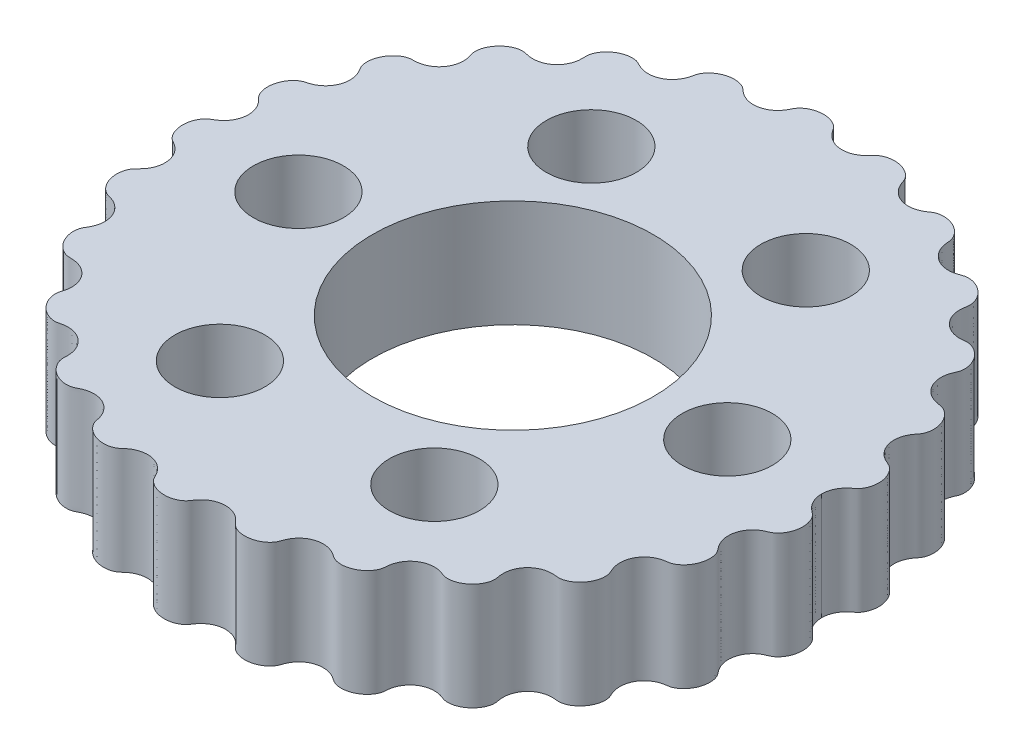
SolidWorks part; units mm, degrees
ref_plane "Front Plane" through (0, 0, 0) normal (0, 0, 1) x (1, 0, 0)
ref_plane "Top Plane" through (0, 0, 0) normal (0, 1, 0) x (1, 0, 0)
ref_plane "Right Plane" through (0, 0, 0) normal (1, 0, 0) x (0, 0, -1)
sketch "Sketch2" plane through (0, 0, 0) normal (0, 1, 0) x (1, 0, 0)
  line L0 (-15.4, 0) -> (14.4, 0) construction
  line L1 (0, 0) -> (0, 14.9128) construction
  line L2 (0, 0) -> (0, -14.9128) construction
  line L3 (0, 0) -> (-0.5, 0) construction
  line L4 (-0.5, 0) -> (-0.5, 15.3103) construction
  line L5 (-0.5, 0) -> (-0.5, -15.3103) construction
  line L6 (14.4, 0) -> (15.5, 0) construction
  line L7 (0, 0) -> (10, 0) construction
  line L8 (7.9, 0) -> (9.5, 0)
  line L9 (-0.5, 0) -> (9.5, 0) construction
  circle A0 centre (-0.5, 0) radius 16
  circle A1 centre (15.5, 0) radius 1
  circle A2 centre (15.0351, -3.8291) radius 1
  circle A3 centre (13.6673, -7.4356) radius 1
  circle A4 centre (11.4762, -10.61) radius 1
  circle A5 centre (8.589, -13.1677) radius 1
  circle A6 centre (5.1737, -14.9603) radius 1
  circle A7 centre (1.4286, -15.8833) radius 1
  circle A8 centre (-2.4286, -15.8833) radius 1
  circle A9 centre (-6.1737, -14.9603) radius 1
  circle A10 centre (-9.589, -13.1677) radius 1
  circle A11 centre (-12.4762, -10.61) radius 1
  circle A12 centre (-14.6673, -7.4356) radius 1
  circle A13 centre (-16.0351, -3.8291) radius 1
  circle A14 centre (-16.5, 0) radius 1
  circle A15 centre (-16.0351, 3.8291) radius 1
  circle A16 centre (-14.6673, 7.4356) radius 1
  circle A17 centre (-12.4762, 10.61) radius 1
  circle A18 centre (-9.589, 13.1677) radius 1
  circle A19 centre (-6.1737, 14.9603) radius 1
  circle A20 centre (-2.4286, 15.8833) radius 1
  circle A21 centre (1.4286, 15.8833) radius 1
  circle A22 centre (5.1737, 14.9603) radius 1
  circle A23 centre (8.589, 13.1677) radius 1
  circle A24 centre (11.4762, 10.61) radius 1
  circle A25 centre (13.6673, 7.4356) radius 1
  circle A26 centre (15.0351, 3.8291) radius 1
  circle A27 centre (0, 0) radius 10
  circle A28 centre (10, 0) radius 2.1
  circle A29 centre (5, -8.6603) radius 2.1
  circle A30 centre (-5, -8.6603) radius 2.1
  circle A31 centre (-10, 0) radius 2.1
  circle A32 centre (-5, 8.6603) radius 2.1
  circle A33 centre (5, 8.6603) radius 2.1
  circle A34 centre (-6, 8.6603) radius 2.1
  circle A35 centre (4, 8.6603) radius 2.1
  circle A36 centre (9, 0) radius 2.1
  circle A37 centre (4, -8.6603) radius 2.1
  circle A38 centre (-6, -8.6603) radius 2.1
  circle A39 centre (-1, 0) radius 10
  circle A40 centre (-11, 0) radius 2.1
  circle A41 centre (9.5, 0) radius 1.5
  circle A42 centre (4.5, -8.6603) radius 1.5
  circle A43 centre (-5.5, -8.6603) radius 1.5
  circle A44 centre (-10.5, 0) radius 1.5
  circle A45 centre (-5.5, 8.6603) radius 1.5
  circle A46 centre (4.5, 8.6603) radius 1.5
  circle A47 centre (0, 0) radius 5.55
  spline S0 degree 4 poles (14.1521, 3.1658) (14.188, 3.1199) (14.2658, 3.0332) (14.3775, 2.9384) (14.515, 2.8555) (14.6203, 2.806) (14.6874, 2.778) (14.7412, 2.7556) (14.7939, 2.7309) (14.8442, 2.7016) (14.9616, 2.6171) (15.116, 2.4418) (15.2531, 2.163) (15.3044, 1.8261) (15.2781, 1.5454) (15.2134, 1.3341) (15.1457, 1.199) (15.0717, 1.0959) (14.999, 1.0246) (14.9346, 0.9749) (14.8529, 0.9144) (14.7598, 0.8351) (14.6613, 0.7318) (14.5658, 0.5985) (14.4899, 0.4547) (14.4445, 0.3242) (14.4198, 0.2202) (14.4058, 0.1237) (14.3997, 0.036) (14.399, -0.0233) (14.4055, -0.1232) (14.4175, -0.2057) (14.4353, -0.2848) (14.4589, -0.3638) (14.4955, -0.4601) (14.5538, -0.5777) (14.629, -0.6905) (14.7205, -0.7952) (14.8099, -0.8785) (14.886, -0.9397) (14.9653, -0.9969) (15.0394, -1.0608) (15.1018, -1.1365) (15.1543, -1.2193) (15.2086, -1.3292) (15.2563, -1.4688) (15.2881, -1.6381) (15.2945, -1.881) (15.2523, -2.1199) (15.1638, -2.3444) (15.0424, -2.5231) (14.9425, -2.6287) (14.8453, -2.7036) (14.7572, -2.7504) (14.6644, -2.7867) (14.5734, -2.827) (14.4636, -2.8857) (14.309, -2.9902) (14.1305, -3.1658) (13.9721, -3.435) (13.894, -3.7733) (13.9169, -4.0803) (13.9952, -4.3102) (14.0824, -4.4685) (14.1503, -4.5677) (14.21, -4.6429) (14.2706, -4.7176) (14.3202, -4.8002) (14.3654, -4.9109) (14.3993, -5.0496) (14.4169, -5.2624) (14.3843, -5.5009) (14.3041, -5.731) (14.178, -5.9418) (14.0479, -6.0957) (13.9108, -6.2086) (13.7771, -6.2844) (13.6546, -6.3259) (13.5506, -6.3413) (13.4467, -6.3556) (13.3441, -6.3782) (13.2186, -6.4164) (13.0491, -6.4902) (12.8504, -6.6239) (12.6494, -6.8484) (12.5061, -7.1523) (12.463, -7.451) (12.49, -7.6921) (12.5392, -7.8624) (12.5803, -7.968) (12.6183, -8.0504) (12.6544, -8.1336) (12.6783, -8.2214) (12.6929, -8.336) (12.6907, -8.4762) (12.6543, -8.6855) (12.5452, -8.9512) (12.3731, -9.1837) (12.1492, -9.3663) (11.9533, -9.4633) (11.8116, -9.5062) (11.6867, -9.5225) (11.5835, -9.517) (11.4812, -9.5034) (11.3782, -9.4969) (11.2749, -9.4982) (11.1721, -9.508) (11.0085, -9.5382) (10.791, -9.6158) (10.5438, -9.7787) (10.3474, -10.0243) (10.2402, -10.2686) (10.1943, -10.4842) (10.1853, -10.6384) (10.1931, -10.7705) (10.2091, -10.8795) (10.2256, -10.9662) (10.236, -11.0539) (10.2331, -11.1423) (10.2158, -11.2534) (10.1767, -11.3842) (10.0886, -11.5718) (9.9146, -11.8006) (9.6439, -12.0158) (9.3384, -12.1314) (9.0923, -12.1519) (8.9388, -12.1247) (8.8741, -12.1049) (8.8233, -12.0863) (8.76, -12.0622) (8.6577, -12.0268) (8.5127, -11.9913) (8.2954, -11.971) (8.0233, -12.0058) (7.7397, -12.12) (7.4775, -12.3303) (7.3093, -12.5758) (7.2277, -12.7964) (7.1948, -12.9647) (7.1831, -13.0729) (7.1774, -13.16) (7.1639, -13.2682) (7.1207, -13.3961) (7.0432, -13.5357) (6.8963, -13.7154) (6.6678, -13.8963) (6.3478, -14.0387) (6.02, -14.0727) (5.7619, -14.0269) (5.5985, -13.9438) (5.5126, -13.8801) (5.4018, -13.8057) (5.2599, -13.7303) (5.0524, -13.6565) (4.7738, -13.623) (4.4626, -13.6683) (4.1888, -13.7999) (3.9912, -13.9665) (3.8578, -14.1339) (3.7826, -14.2632) (3.7309, -14.3799) (3.6959, -14.48) (3.6689, -14.5606) (3.6251, -14.6573) (3.5494, -14.7647) (3.44, -14.8752) (3.2557, -15.006) (2.9928, -15.1201) (2.6515, -15.1757) (2.3406, -15.1291) (2.1258, -15.0338) (2.011, -14.9468) (1.9698, -14.909) (1.9317, -14.8681) (1.8954, -14.8255) (1.8499, -14.7726) (1.7735, -14.691) (1.6576, -14.5893) (1.4677, -14.4687) (1.2013, -14.3748) (0.8943, -14.3518) (0.5705, -14.4236) (0.3173, -14.5632) (0.1515, -14.7141) (0.0481, -14.8418) (-0.0114, -14.9289) (-0.057, -15) (-0.1205, -15.0845) (-0.2167, -15.1711) (-0.3455, -15.2521) (-0.5484, -15.3356) (-0.8128, -15.3854) (-1.084, -15.3726) (-1.345, -15.2972) (-1.5435, -15.1922) (-1.6658, -15.0976) (-1.7547, -15.002) (-1.8112, -14.9128) (-1.8483, -14.8369) (-1.8948, -14.7422) (-1.9811, -14.5964) (-2.1305, -14.4153) (-2.3717, -14.2374) (-2.6941, -14.1243) (-3.0058, -14.1121) (-3.2798, -14.1742) (-3.4814, -14.2713) (-3.6077, -14.3581) (-3.6929, -14.4296) (-3.7443, -14.4763) (-3.7855, -14.5136) (-3.839, -14.5578) (-3.9718, -14.6426) (-4.2092, -14.7163) (-4.5379, -14.7232) (-4.871, -14.6233) (-5.1192, -14.4741) (-5.2872, -14.3161) (-5.3818, -14.1887) (-5.4416, -14.0686) (-5.4698, -13.9639) (-5.4862, -13.8788) (-5.5106, -13.7734) (-5.5628, -13.6112) (-5.6686, -13.4029) (-5.8615, -13.1808) (-6.1409, -13.0036) (-6.4324, -12.9205) (-6.707, -12.9139) (-6.9246, -12.958) (-7.0705, -13.0119) (-7.1719, -13.0612) (-7.2342, -13.0943) (-7.2842, -13.1203) (-7.3485, -13.1494) (-7.4504, -13.1813) (-7.5929, -13.1993) (-7.8225, -13.1875) (-8.1082, -13.1019) (-8.3607, -12.9481) (-8.5641, -12.7393) (-8.6869, -12.541) (-8.7459, -12.3913) (-8.7711, -12.2579) (-8.7697, -12.1482) (-8.7645, -12.0606) (-8.7633, -11.951) (-8.7731, -11.8212) (-8.8019, -11.6732) (-8.8729, -11.4717) (-9.0045, -11.25) (-9.2205, -11.0351) (-9.4997, -10.8905) (-9.7475, -10.8369) (-9.9383, -10.8322) (-10.0675, -10.8437) (-10.1698, -10.8609) (-10.2704, -10.8859) (-10.3717, -10.9089) (-10.4995, -10.9144) (-10.6499, -10.893) (-10.8644, -10.8236) (-11.1154, -10.6702) (-11.3185, -10.4608) (-11.4614, -10.2119) (-11.5248, -10.0134) (-11.5464, -9.8777) (-11.5487, -9.7646) (-11.5393, -9.6761) (-11.5169, -9.5902) (-11.4896, -9.5058) (-11.4606, -9.3988) (-11.4371, -9.2678) (-11.428, -9.1126) (-11.4489, -8.8917) (-11.5253, -8.6444) (-11.6806, -8.3917) (-11.9083, -8.1893) (-12.1461, -8.0664) (-12.3515, -8.0112) (-12.509, -7.9918) (-12.6408, -7.9895) (-12.7466, -7.9882) (-12.8744, -7.9638) (-13.0178, -7.9059) (-13.1692, -7.8114) (-13.319, -7.6747) (-13.472, -7.4805) (-13.5815, -7.2609) (-13.644, -7.0266) (-13.6529, -6.8129) (-13.6365, -6.6728) (-13.6064, -6.5605) (-13.5704, -6.4764) (-13.5232, -6.3982) (-13.4752, -6.3206) (-13.4215, -6.2199) (-13.3522, -6.0556) (-13.2972, -5.8178) (-13.3061, -5.5112) (-13.4183, -5.1858) (-13.5996, -4.9373) (-13.7884, -4.7826) (-13.9504, -4.6931) (-14.068, -4.6441) (-14.1647, -4.6121) (-14.2634, -4.587) (-14.3606, -4.5562) (-14.4721, -4.4972) (-14.5906, -4.4054) (-14.7415, -4.2409) (-14.8856, -3.984) (-14.9605, -3.7) (-14.9625, -3.4094) (-14.9171, -3.1994) (-14.8649, -3.0655) (-14.8048, -2.9613) (-14.7437, -2.886) (-14.6735, -2.8194) (-14.6048, -2.7515) (-14.5411, -2.6786) (-14.4829, -2.6013) (-14.3984, -2.4684) (-14.3099, -2.2678) (-14.2572, -1.9916) (-14.2948, -1.6527) (-14.4157, -1.3725) (-14.5648, -1.1806) (-14.7009, -1.0585) (-14.8015, -0.9857) (-14.886, -0.9336) (-14.9732, -0.8861) (-15.056, -0.8309) (-15.1453, -0.7457) (-15.2341, -0.6279) (-15.3021, -0.4979) (-15.3506, -0.3595) (-15.3784, -0.2422) (-15.3932, -0.1473) (-15.4005, -0.0379) (-15.4007, 0.0312) (-15.3943, 0.133) (-15.3819, 0.2227) (-15.3632, 0.3082) (-15.3383, 0.3938) (-15.2991, 0.498) (-15.241, 0.614) (-15.1569, 0.7356) (-15.0521, 0.8388) (-14.947, 0.9) (-14.8417, 0.9596) (-14.7374, 1.0292) (-14.6222, 1.1253) (-14.4762, 1.2888) (-14.3483, 1.5104) (-14.2696, 1.788) (-14.2718, 2.0824) (-14.3338, 2.3297) (-14.4228, 2.5131) (-14.5089, 2.6398) (-14.5912, 2.7371) (-14.6628, 2.8095) (-14.7315, 2.8736) (-14.7874, 2.9388) (-14.8392, 3.0187) (-14.9, 3.1445) (-14.933, 3.2628) (-14.9484, 3.3663) (-14.9531, 3.4358) knots 0 0 0 0 0 0.003662 0.007324 0.009155 0.010071 0.010986 0.011902 0.012818 0.013733 0.014649 0.020984 0.02732 0.032959 0.035778 0.038598 0.041156 0.042436 0.043715 0.044995 0.046274 0.048833 0.051398 0.053964 0.05653 0.059096 0.059963 0.060831 0.062566 0.06386 0.065154 0.066448 0.067743 0.069037 0.070331 0.072919 0.075992 0.077529 0.079065 0.080602 0.082139 0.083675 0.085212 0.086754 0.088296 0.09138 0.094464 0.097548 0.103529 0.106519 0.10951 0.111075 0.112641 0.114207 0.115773 0.117339 0.118905 0.122036 0.127492 0.132948 0.138255 0.143562 0.146585 0.148096 0.149608 0.151119 0.15263 0.154142 0.155653 0.158618 0.161583 0.167513 0.170668 0.173824 0.176979 0.180135 0.181785 0.183435 0.185086 0.186736 0.188387 0.190037 0.193338 0.198334 0.203329 0.208757 0.214186 0.217039 0.218465 0.219892 0.221319 0.222745 0.224172 0.225598 0.228568 0.231538 0.237477 0.243509 0.246525 0.249541 0.251164 0.252787 0.25441 0.256033 0.257656 0.259279 0.260902 0.262525 0.268116 0.273708 0.279232 0.281995 0.284757 0.287531 0.288919 0.290306 0.291693 0.293081 0.294468 0.295855 0.298752 0.301648 0.307441 0.313806 0.320171 0.321875 0.322726 0.323578 0.32443 0.325282 0.326985 0.330392 0.333799 0.338942 0.344084 0.349371 0.354658 0.3574 0.358771 0.360142 0.361513 0.362884 0.365627 0.368572 0.371516 0.377406 0.383828 0.390249 0.39193 0.393611 0.395291 0.396972 0.400333 0.403695 0.409076 0.414457 0.419833 0.422521 0.425209 0.427878 0.429213 0.430548 0.431883 0.433218 0.435887 0.438758 0.441629 0.44737 0.453781 0.460191 0.46107 0.46195 0.462829 0.463708 0.464587 0.465466 0.467225 0.470742 0.474259 0.479542 0.484825 0.489836 0.494847 0.497504 0.498832 0.500161 0.501489 0.502818 0.505475 0.508247 0.51102 0.516564 0.52227 0.525123 0.527976 0.530631 0.531959 0.533286 0.534614 0.535941 0.538597 0.543936 0.549276 0.554531 0.559787 0.563284 0.566782 0.568531 0.569405 0.570279 0.571154 0.572028 0.573777 0.580153 0.586529 0.592383 0.595311 0.598238 0.600963 0.602326 0.603688 0.605051 0.606414 0.609139 0.614393 0.619646 0.62466 0.629675 0.633224 0.636772 0.638547 0.639434 0.640321 0.641208 0.642095 0.64387 0.647026 0.650182 0.656494 0.66242 0.665383 0.668345 0.671105 0.672484 0.673864 0.675243 0.676623 0.679382 0.682041 0.684701 0.690021 0.695473 0.700926 0.704188 0.705819 0.70745 0.709081 0.710712 0.712344 0.713975 0.717095 0.720216 0.726458 0.732287 0.735201 0.738116 0.739511 0.740907 0.742302 0.743698 0.745093 0.746488 0.749279 0.752059 0.754839 0.760398 0.765424 0.770449 0.773769 0.777088 0.778748 0.780408 0.782068 0.783727 0.786901 0.790075 0.793249 0.796422 0.802397 0.805385 0.808372 0.809808 0.811244 0.812679 0.814115 0.81555 0.816986 0.819857 0.825318 0.830779 0.83599 0.841201 0.844404 0.846006 0.847607 0.849209 0.850811 0.852412 0.854014 0.857107 0.8602 0.866387 0.872353 0.875336 0.878319 0.87984 0.881361 0.882882 0.884402 0.885923 0.887444 0.888965 0.890486 0.895823 0.90116 0.906397 0.911634 0.914757 0.916319 0.91788 0.919441 0.921003 0.922564 0.924126 0.927182 0.930238 0.931767 0.933295 0.934823 0.936351 0.937751 0.93915 0.940549 0.941949 0.943348 0.944747 0.947546 0.950087 0.952628 0.953898 0.955168 0.957709 0.960509 0.96331 0.96891 0.973663 0.978415 0.981621 0.984826 0.986428 0.988031 0.989634 0.991236 0.992332 0.993427 0.995618 1 1 1 1 1 construction
  spline S1 degree 4 poles (14.4, 0) (14.4, -0.018) (14.401, -0.0542) (14.4055, -0.1232) (14.4175, -0.2057) (14.4353, -0.2848) (14.4589, -0.3638) (14.4955, -0.4601) (14.5538, -0.5777) (14.629, -0.6905) (14.7205, -0.7952) (14.8099, -0.8785) (14.886, -0.9397) (14.9653, -0.9969) (15.0394, -1.0608) (15.1018, -1.1365) (15.1543, -1.2193) (15.2086, -1.3292) (15.2563, -1.4688) (15.2881, -1.6381) (15.2945, -1.881) (15.2523, -2.1199) (15.1638, -2.3444) (15.0424, -2.5231) (14.9425, -2.6287) (14.8453, -2.7036) (14.7572, -2.7504) (14.6644, -2.7867) (14.5734, -2.827) (14.4636, -2.8857) (14.309, -2.9902) (14.1305, -3.1658) (13.9721, -3.435) (13.894, -3.7733) (13.9169, -4.0803) (13.9952, -4.3102) (14.0824, -4.4685) (14.1503, -4.5677) (14.21, -4.6429) (14.2706, -4.7176) (14.3202, -4.8002) (14.3654, -4.9109) (14.3993, -5.0496) (14.4169, -5.2624) (14.3843, -5.5009) (14.3041, -5.731) (14.178, -5.9418) (14.0479, -6.0957) (13.9108, -6.2086) (13.7771, -6.2844) (13.6546, -6.3259) (13.5506, -6.3413) (13.4467, -6.3556) (13.3441, -6.3782) (13.2186, -6.4164) (13.0491, -6.4902) (12.8504, -6.6239) (12.6494, -6.8484) (12.5061, -7.1523) (12.463, -7.451) (12.49, -7.6921) (12.5392, -7.8624) (12.5803, -7.968) (12.6183, -8.0504) (12.6544, -8.1336) (12.6783, -8.2214) (12.6929, -8.336) (12.6907, -8.4762) (12.6543, -8.6855) (12.5452, -8.9512) (12.3731, -9.1837) (12.1492, -9.3663) (11.9533, -9.4633) (11.8116, -9.5062) (11.6867, -9.5225) (11.5835, -9.517) (11.4812, -9.5034) (11.3782, -9.4969) (11.2749, -9.4982) (11.1721, -9.508) (11.0085, -9.5382) (10.791, -9.6158) (10.5438, -9.7787) (10.3474, -10.0243) (10.2402, -10.2686) (10.1943, -10.4842) (10.1853, -10.6384) (10.1931, -10.7705) (10.2091, -10.8795) (10.2256, -10.9662) (10.236, -11.0539) (10.2331, -11.1423) (10.2158, -11.2534) (10.1767, -11.3842) (10.0886, -11.5718) (9.9146, -11.8006) (9.6439, -12.0158) (9.3384, -12.1314) (9.0923, -12.1519) (8.9388, -12.1247) (8.8741, -12.1049) (8.8233, -12.0863) (8.76, -12.0622) (8.6577, -12.0268) (8.5127, -11.9913) (8.2954, -11.971) (8.0233, -12.0058) (7.7397, -12.12) (7.4775, -12.3303) (7.3093, -12.5758) (7.2277, -12.7964) (7.1948, -12.9647) (7.1831, -13.0729) (7.1774, -13.16) (7.1639, -13.2682) (7.1207, -13.3961) (7.0432, -13.5357) (6.8963, -13.7154) (6.6678, -13.8963) (6.3478, -14.0387) (6.02, -14.0727) (5.7619, -14.0269) (5.5985, -13.9438) (5.5126, -13.8801) (5.4018, -13.8057) (5.2599, -13.7303) (5.0524, -13.6565) (4.7738, -13.623) (4.4626, -13.6683) (4.1888, -13.7999) (3.9912, -13.9665) (3.8578, -14.1339) (3.7826, -14.2632) (3.7309, -14.3799) (3.6959, -14.48) (3.6689, -14.5606) (3.6251, -14.6573) (3.5494, -14.7647) (3.44, -14.8752) (3.2557, -15.006) (2.9928, -15.1201) (2.6515, -15.1757) (2.3406, -15.1291) (2.1258, -15.0338) (2.011, -14.9468) (1.9698, -14.909) (1.9317, -14.8681) (1.8954, -14.8255) (1.8499, -14.7726) (1.7735, -14.691) (1.6576, -14.5893) (1.4677, -14.4687) (1.2013, -14.3748) (0.8943, -14.3518) (0.5705, -14.4236) (0.3173, -14.5632) (0.1515, -14.7141) (0.0481, -14.8418) (-0.0114, -14.9289) (-0.057, -15) (-0.1205, -15.0845) (-0.2167, -15.1711) (-0.3455, -15.2521) (-0.5484, -15.3356) (-0.8128, -15.3854) (-1.084, -15.3726) (-1.345, -15.2972) (-1.5435, -15.1922) (-1.6658, -15.0976) (-1.7547, -15.002) (-1.8112, -14.9128) (-1.8483, -14.8369) (-1.8948, -14.7422) (-1.9811, -14.5964) (-2.1305, -14.4153) (-2.3717, -14.2374) (-2.6941, -14.1243) (-3.0058, -14.1121) (-3.2798, -14.1742) (-3.4814, -14.2713) (-3.6077, -14.3581) (-3.6929, -14.4296) (-3.7443, -14.4763) (-3.7855, -14.5136) (-3.839, -14.5578) (-3.9718, -14.6426) (-4.2092, -14.7163) (-4.5379, -14.7232) (-4.871, -14.6233) (-5.1192, -14.4741) (-5.2872, -14.3161) (-5.3818, -14.1887) (-5.4416, -14.0686) (-5.4698, -13.9639) (-5.4862, -13.8788) (-5.5106, -13.7734) (-5.5628, -13.6112) (-5.6686, -13.4029) (-5.8615, -13.1808) (-6.1409, -13.0036) (-6.4324, -12.9205) (-6.707, -12.9139) (-6.9246, -12.958) (-7.0705, -13.0119) (-7.1719, -13.0612) (-7.2342, -13.0943) (-7.2842, -13.1203) (-7.3485, -13.1494) (-7.4504, -13.1813) (-7.5929, -13.1993) (-7.8225, -13.1875) (-8.1082, -13.1019) (-8.3607, -12.9481) (-8.5641, -12.7393) (-8.6869, -12.541) (-8.7459, -12.3913) (-8.7711, -12.2579) (-8.7697, -12.1482) (-8.7645, -12.0606) (-8.7633, -11.951) (-8.7731, -11.8212) (-8.8019, -11.6732) (-8.8729, -11.4717) (-9.0045, -11.25) (-9.2205, -11.0351) (-9.4997, -10.8905) (-9.7475, -10.8369) (-9.9383, -10.8322) (-10.0675, -10.8437) (-10.1698, -10.8609) (-10.2704, -10.8859) (-10.3717, -10.9089) (-10.4995, -10.9144) (-10.6499, -10.893) (-10.8644, -10.8236) (-11.1154, -10.6702) (-11.3185, -10.4608) (-11.4614, -10.2119) (-11.5248, -10.0134) (-11.5464, -9.8777) (-11.5487, -9.7646) (-11.5393, -9.6761) (-11.5169, -9.5902) (-11.4896, -9.5058) (-11.4606, -9.3988) (-11.4371, -9.2678) (-11.428, -9.1126) (-11.4489, -8.8917) (-11.5253, -8.6444) (-11.6806, -8.3917) (-11.9083, -8.1893) (-12.1461, -8.0664) (-12.3515, -8.0112) (-12.509, -7.9918) (-12.6408, -7.9895) (-12.7466, -7.9882) (-12.8744, -7.9638) (-13.0178, -7.9059) (-13.1692, -7.8114) (-13.319, -7.6747) (-13.472, -7.4805) (-13.5815, -7.2609) (-13.644, -7.0266) (-13.6529, -6.8129) (-13.6365, -6.6728) (-13.6064, -6.5605) (-13.5704, -6.4764) (-13.5232, -6.3982) (-13.4752, -6.3206) (-13.4215, -6.2199) (-13.3522, -6.0556) (-13.2972, -5.8178) (-13.3061, -5.5112) (-13.4183, -5.1858) (-13.5996, -4.9373) (-13.7884, -4.7826) (-13.9504, -4.6931) (-14.068, -4.6441) (-14.1647, -4.6121) (-14.2634, -4.587) (-14.3606, -4.5562) (-14.4721, -4.4972) (-14.5906, -4.4054) (-14.7415, -4.2409) (-14.8856, -3.984) (-14.9605, -3.7) (-14.9625, -3.4094) (-14.9171, -3.1994) (-14.8649, -3.0655) (-14.8048, -2.9613) (-14.7437, -2.886) (-14.6735, -2.8194) (-14.6048, -2.7515) (-14.5411, -2.6786) (-14.4829, -2.6013) (-14.3984, -2.4684) (-14.3099, -2.2678) (-14.2572, -1.9916) (-14.2948, -1.6527) (-14.4157, -1.3725) (-14.5648, -1.1806) (-14.7009, -1.0585) (-14.8015, -0.9857) (-14.886, -0.9336) (-14.9732, -0.8861) (-15.056, -0.8309) (-15.1453, -0.7457) (-15.2341, -0.6279) (-15.3021, -0.4979) (-15.3506, -0.3595) (-15.3784, -0.2422) (-15.3932, -0.1473) (-15.3988, -0.0635) (-15.4, -0.0212) (-15.4, 0) knots 0.062566 0.062566 0.062566 0.062566 0.062566 0.06386 0.065154 0.066448 0.067743 0.069037 0.070331 0.072919 0.075992 0.077529 0.079065 0.080602 0.082139 0.083675 0.085212 0.086754 0.088296 0.09138 0.094464 0.097548 0.103529 0.106519 0.10951 0.111075 0.112641 0.114207 0.115773 0.117339 0.118905 0.122036 0.127492 0.132948 0.138255 0.143562 0.146585 0.148096 0.149608 0.151119 0.15263 0.154142 0.155653 0.158618 0.161583 0.167513 0.170668 0.173824 0.176979 0.180135 0.181785 0.183435 0.185086 0.186736 0.188387 0.190037 0.193338 0.198334 0.203329 0.208757 0.214186 0.217039 0.218465 0.219892 0.221319 0.222745 0.224172 0.225598 0.228568 0.231538 0.237477 0.243509 0.246525 0.249541 0.251164 0.252787 0.25441 0.256033 0.257656 0.259279 0.260902 0.262525 0.268116 0.273708 0.279232 0.281995 0.284757 0.287531 0.288919 0.290306 0.291693 0.293081 0.294468 0.295855 0.298752 0.301648 0.307441 0.313806 0.320171 0.321875 0.322726 0.323578 0.32443 0.325282 0.326985 0.330392 0.333799 0.338942 0.344084 0.349371 0.354658 0.3574 0.358771 0.360142 0.361513 0.362884 0.365627 0.368572 0.371516 0.377406 0.383828 0.390249 0.39193 0.393611 0.395291 0.396972 0.400333 0.403695 0.409076 0.414457 0.419833 0.422521 0.425209 0.427878 0.429213 0.430548 0.431883 0.433218 0.435887 0.438758 0.441629 0.44737 0.453781 0.460191 0.46107 0.46195 0.462829 0.463708 0.464587 0.465466 0.467225 0.470742 0.474259 0.479542 0.484825 0.489836 0.494847 0.497504 0.498832 0.500161 0.501489 0.502818 0.505475 0.508247 0.51102 0.516564 0.52227 0.525123 0.527976 0.530631 0.531959 0.533286 0.534614 0.535941 0.538597 0.543936 0.549276 0.554531 0.559787 0.563284 0.566782 0.568531 0.569405 0.570279 0.571154 0.572028 0.573777 0.580153 0.586529 0.592383 0.595311 0.598238 0.600963 0.602326 0.603688 0.605051 0.606414 0.609139 0.614393 0.619646 0.62466 0.629675 0.633224 0.636772 0.638547 0.639434 0.640321 0.641208 0.642095 0.64387 0.647026 0.650182 0.656494 0.66242 0.665383 0.668345 0.671105 0.672484 0.673864 0.675243 0.676623 0.679382 0.682041 0.684701 0.690021 0.695473 0.700926 0.704188 0.705819 0.70745 0.709081 0.710712 0.712344 0.713975 0.717095 0.720216 0.726458 0.732287 0.735201 0.738116 0.739511 0.740907 0.742302 0.743698 0.745093 0.746488 0.749279 0.752059 0.754839 0.760398 0.765424 0.770449 0.773769 0.777088 0.778748 0.780408 0.782068 0.783727 0.786901 0.790075 0.793249 0.796422 0.802397 0.805385 0.808372 0.809808 0.811244 0.812679 0.814115 0.81555 0.816986 0.819857 0.825318 0.830779 0.83599 0.841201 0.844404 0.846006 0.847607 0.849209 0.850811 0.852412 0.854014 0.857107 0.8602 0.866387 0.872353 0.875336 0.878319 0.87984 0.881361 0.882882 0.884402 0.885923 0.887444 0.888965 0.890486 0.895823 0.90116 0.906397 0.911634 0.914757 0.916319 0.91788 0.919441 0.921003 0.922564 0.924126 0.927182 0.930238 0.931767 0.933295 0.934823 0.936351 0.936351 0.936351 0.936351 0.936351
  spline S2 degree 4 poles (14.4, 0) (14.4, 0.018) (14.401, 0.0542) (14.4055, 0.1232) (14.4175, 0.2057) (14.4353, 0.2848) (14.4589, 0.3638) (14.4955, 0.4601) (14.5538, 0.5777) (14.629, 0.6905) (14.7205, 0.7952) (14.8099, 0.8785) (14.886, 0.9397) (14.9653, 0.9969) (15.0394, 1.0608) (15.1018, 1.1365) (15.1543, 1.2193) (15.2086, 1.3292) (15.2563, 1.4688) (15.2881, 1.6381) (15.2945, 1.881) (15.2523, 2.1199) (15.1638, 2.3444) (15.0424, 2.5231) (14.9425, 2.6287) (14.8453, 2.7036) (14.7572, 2.7504) (14.6644, 2.7867) (14.5734, 2.827) (14.4636, 2.8857) (14.309, 2.9902) (14.1305, 3.1658) (13.9721, 3.435) (13.894, 3.7733) (13.9169, 4.0803) (13.9952, 4.3102) (14.0824, 4.4685) (14.1503, 4.5677) (14.21, 4.6429) (14.2706, 4.7176) (14.3202, 4.8002) (14.3654, 4.9109) (14.3993, 5.0496) (14.4169, 5.2624) (14.3843, 5.5009) (14.3041, 5.731) (14.178, 5.9418) (14.0479, 6.0957) (13.9108, 6.2086) (13.7771, 6.2844) (13.6546, 6.3259) (13.5506, 6.3413) (13.4467, 6.3556) (13.3441, 6.3782) (13.2186, 6.4164) (13.0491, 6.4902) (12.8504, 6.6239) (12.6494, 6.8484) (12.5061, 7.1523) (12.463, 7.451) (12.49, 7.6921) (12.5392, 7.8624) (12.5803, 7.968) (12.6183, 8.0504) (12.6544, 8.1336) (12.6783, 8.2214) (12.6929, 8.336) (12.6907, 8.4762) (12.6543, 8.6855) (12.5452, 8.9512) (12.3731, 9.1837) (12.1492, 9.3663) (11.9533, 9.4633) (11.8116, 9.5062) (11.6867, 9.5225) (11.5835, 9.517) (11.4812, 9.5034) (11.3782, 9.4969) (11.2749, 9.4982) (11.1721, 9.508) (11.0085, 9.5382) (10.791, 9.6158) (10.5438, 9.7787) (10.3474, 10.0243) (10.2402, 10.2686) (10.1943, 10.4842) (10.1853, 10.6384) (10.1931, 10.7705) (10.2091, 10.8795) (10.2256, 10.9662) (10.236, 11.0539) (10.2331, 11.1423) (10.2158, 11.2534) (10.1767, 11.3842) (10.0886, 11.5718) (9.9146, 11.8006) (9.6439, 12.0158) (9.3384, 12.1314) (9.0923, 12.1519) (8.9388, 12.1247) (8.8741, 12.1049) (8.8233, 12.0863) (8.76, 12.0622) (8.6577, 12.0268) (8.5127, 11.9913) (8.2954, 11.971) (8.0233, 12.0058) (7.7397, 12.12) (7.4775, 12.3303) (7.3093, 12.5758) (7.2277, 12.7964) (7.1948, 12.9647) (7.1831, 13.0729) (7.1774, 13.16) (7.1639, 13.2682) (7.1207, 13.3961) (7.0432, 13.5357) (6.8963, 13.7154) (6.6678, 13.8963) (6.3478, 14.0387) (6.02, 14.0727) (5.7619, 14.0269) (5.5985, 13.9438) (5.5126, 13.8801) (5.4018, 13.8057) (5.2599, 13.7303) (5.0524, 13.6565) (4.7738, 13.623) (4.4626, 13.6683) (4.1888, 13.7999) (3.9912, 13.9665) (3.8578, 14.1339) (3.7826, 14.2632) (3.7309, 14.3799) (3.6959, 14.48) (3.6689, 14.5606) (3.6251, 14.6573) (3.5494, 14.7647) (3.44, 14.8752) (3.2557, 15.006) (2.9928, 15.1201) (2.6515, 15.1757) (2.3406, 15.1291) (2.1258, 15.0338) (2.011, 14.9468) (1.9698, 14.909) (1.9317, 14.8681) (1.8954, 14.8255) (1.8499, 14.7726) (1.7735, 14.691) (1.6576, 14.5893) (1.4677, 14.4687) (1.2013, 14.3748) (0.8943, 14.3518) (0.5705, 14.4236) (0.3173, 14.5632) (0.1515, 14.7141) (0.0481, 14.8418) (-0.0114, 14.9289) (-0.057, 15) (-0.1205, 15.0845) (-0.2167, 15.1711) (-0.3455, 15.2521) (-0.5484, 15.3356) (-0.8128, 15.3854) (-1.084, 15.3726) (-1.345, 15.2972) (-1.5435, 15.1922) (-1.6658, 15.0976) (-1.7547, 15.002) (-1.8112, 14.9128) (-1.8483, 14.8369) (-1.8948, 14.7422) (-1.9811, 14.5964) (-2.1305, 14.4153) (-2.3717, 14.2374) (-2.6941, 14.1243) (-3.0058, 14.1121) (-3.2798, 14.1742) (-3.4814, 14.2713) (-3.6077, 14.3581) (-3.6929, 14.4296) (-3.7443, 14.4763) (-3.7855, 14.5136) (-3.839, 14.5578) (-3.9718, 14.6426) (-4.2092, 14.7163) (-4.5379, 14.7232) (-4.871, 14.6233) (-5.1192, 14.4741) (-5.2872, 14.3161) (-5.3818, 14.1887) (-5.4416, 14.0686) (-5.4698, 13.9639) (-5.4862, 13.8788) (-5.5106, 13.7734) (-5.5628, 13.6112) (-5.6686, 13.4029) (-5.8615, 13.1808) (-6.1409, 13.0036) (-6.4324, 12.9205) (-6.707, 12.9139) (-6.9246, 12.958) (-7.0705, 13.0119) (-7.1719, 13.0612) (-7.2342, 13.0943) (-7.2842, 13.1203) (-7.3485, 13.1494) (-7.4504, 13.1813) (-7.5929, 13.1993) (-7.8225, 13.1875) (-8.1082, 13.1019) (-8.3607, 12.9481) (-8.5641, 12.7393) (-8.6869, 12.541) (-8.7459, 12.3913) (-8.7711, 12.2579) (-8.7697, 12.1482) (-8.7645, 12.0606) (-8.7633, 11.951) (-8.7731, 11.8212) (-8.8019, 11.6732) (-8.8729, 11.4717) (-9.0045, 11.25) (-9.2205, 11.0351) (-9.4997, 10.8905) (-9.7475, 10.8369) (-9.9383, 10.8322) (-10.0675, 10.8437) (-10.1698, 10.8609) (-10.2704, 10.8859) (-10.3717, 10.9089) (-10.4995, 10.9144) (-10.6499, 10.893) (-10.8644, 10.8236) (-11.1154, 10.6702) (-11.3185, 10.4608) (-11.4614, 10.2119) (-11.5248, 10.0134) (-11.5464, 9.8777) (-11.5487, 9.7646) (-11.5393, 9.6761) (-11.5169, 9.5902) (-11.4896, 9.5058) (-11.4606, 9.3988) (-11.4371, 9.2678) (-11.428, 9.1126) (-11.4489, 8.8917) (-11.5253, 8.6444) (-11.6806, 8.3917) (-11.9083, 8.1893) (-12.1461, 8.0664) (-12.3515, 8.0112) (-12.509, 7.9918) (-12.6408, 7.9895) (-12.7466, 7.9882) (-12.8744, 7.9638) (-13.0178, 7.9059) (-13.1692, 7.8114) (-13.319, 7.6747) (-13.472, 7.4805) (-13.5815, 7.2609) (-13.644, 7.0266) (-13.6529, 6.8129) (-13.6365, 6.6728) (-13.6064, 6.5605) (-13.5704, 6.4764) (-13.5232, 6.3982) (-13.4752, 6.3206) (-13.4215, 6.2199) (-13.3522, 6.0556) (-13.2972, 5.8178) (-13.3061, 5.5112) (-13.4183, 5.1858) (-13.5996, 4.9373) (-13.7884, 4.7826) (-13.9504, 4.6931) (-14.068, 4.6441) (-14.1647, 4.6121) (-14.2634, 4.587) (-14.3606, 4.5562) (-14.4721, 4.4972) (-14.5906, 4.4054) (-14.7415, 4.2409) (-14.8856, 3.984) (-14.9605, 3.7) (-14.9625, 3.4094) (-14.9171, 3.1994) (-14.8649, 3.0655) (-14.8048, 2.9613) (-14.7437, 2.886) (-14.6735, 2.8194) (-14.6048, 2.7515) (-14.5411, 2.6786) (-14.4829, 2.6013) (-14.3984, 2.4684) (-14.3099, 2.2678) (-14.2572, 1.9916) (-14.2948, 1.6527) (-14.4157, 1.3725) (-14.5648, 1.1806) (-14.7009, 1.0585) (-14.8015, 0.9857) (-14.886, 0.9336) (-14.9732, 0.8861) (-15.056, 0.8309) (-15.1453, 0.7457) (-15.2341, 0.6279) (-15.3021, 0.4979) (-15.3506, 0.3595) (-15.3784, 0.2422) (-15.3932, 0.1473) (-15.3988, 0.0635) (-15.4, 0.0212) (-15.4, 0) knots 0.062566 0.062566 0.062566 0.062566 0.062566 0.06386 0.065154 0.066448 0.067743 0.069037 0.070331 0.072919 0.075992 0.077529 0.079065 0.080602 0.082139 0.083675 0.085212 0.086754 0.088296 0.09138 0.094464 0.097548 0.103529 0.106519 0.10951 0.111075 0.112641 0.114207 0.115773 0.117339 0.118905 0.122036 0.127492 0.132948 0.138255 0.143562 0.146585 0.148096 0.149608 0.151119 0.15263 0.154142 0.155653 0.158618 0.161583 0.167513 0.170668 0.173824 0.176979 0.180135 0.181785 0.183435 0.185086 0.186736 0.188387 0.190037 0.193338 0.198334 0.203329 0.208757 0.214186 0.217039 0.218465 0.219892 0.221319 0.222745 0.224172 0.225598 0.228568 0.231538 0.237477 0.243509 0.246525 0.249541 0.251164 0.252787 0.25441 0.256033 0.257656 0.259279 0.260902 0.262525 0.268116 0.273708 0.279232 0.281995 0.284757 0.287531 0.288919 0.290306 0.291693 0.293081 0.294468 0.295855 0.298752 0.301648 0.307441 0.313806 0.320171 0.321875 0.322726 0.323578 0.32443 0.325282 0.326985 0.330392 0.333799 0.338942 0.344084 0.349371 0.354658 0.3574 0.358771 0.360142 0.361513 0.362884 0.365627 0.368572 0.371516 0.377406 0.383828 0.390249 0.39193 0.393611 0.395291 0.396972 0.400333 0.403695 0.409076 0.414457 0.419833 0.422521 0.425209 0.427878 0.429213 0.430548 0.431883 0.433218 0.435887 0.438758 0.441629 0.44737 0.453781 0.460191 0.46107 0.46195 0.462829 0.463708 0.464587 0.465466 0.467225 0.470742 0.474259 0.479542 0.484825 0.489836 0.494847 0.497504 0.498832 0.500161 0.501489 0.502818 0.505475 0.508247 0.51102 0.516564 0.52227 0.525123 0.527976 0.530631 0.531959 0.533286 0.534614 0.535941 0.538597 0.543936 0.549276 0.554531 0.559787 0.563284 0.566782 0.568531 0.569405 0.570279 0.571154 0.572028 0.573777 0.580153 0.586529 0.592383 0.595311 0.598238 0.600963 0.602326 0.603688 0.605051 0.606414 0.609139 0.614393 0.619646 0.62466 0.629675 0.633224 0.636772 0.638547 0.639434 0.640321 0.641208 0.642095 0.64387 0.647026 0.650182 0.656494 0.66242 0.665383 0.668345 0.671105 0.672484 0.673864 0.675243 0.676623 0.679382 0.682041 0.684701 0.690021 0.695473 0.700926 0.704188 0.705819 0.70745 0.709081 0.710712 0.712344 0.713975 0.717095 0.720216 0.726458 0.732287 0.735201 0.738116 0.739511 0.740907 0.742302 0.743698 0.745093 0.746488 0.749279 0.752059 0.754839 0.760398 0.765424 0.770449 0.773769 0.777088 0.778748 0.780408 0.782068 0.783727 0.786901 0.790075 0.793249 0.796422 0.802397 0.805385 0.808372 0.809808 0.811244 0.812679 0.814115 0.81555 0.816986 0.819857 0.825318 0.830779 0.83599 0.841201 0.844404 0.846006 0.847607 0.849209 0.850811 0.852412 0.854014 0.857107 0.8602 0.866387 0.872353 0.875336 0.878319 0.87984 0.881361 0.882882 0.884402 0.885923 0.887444 0.888965 0.890486 0.895823 0.90116 0.906397 0.911634 0.914757 0.916319 0.91788 0.919441 0.921003 0.922564 0.924126 0.927182 0.930238 0.931767 0.933295 0.934823 0.936351 0.936351 0.936351 0.936351 0.936351
  dimension "D1" = 32
  dimension "D2" = 2
  dimension "D4" = 20
  dimension "D5" = 4.2
  dimension "D8" = 6
  dimension "D7" = 10
  dimension "D9" = 10
  dimension "D3" = 26
  dimension "D6" = 6
extrude "Boss-Extrude1" add sketch "Sketch2" along normal blind 5 contours S1 S2
sketch "Sketch3" plane through (0, 0, 0) normal (0, 1, 0) x (1, 0, 0)
  circle A0 centre (10, 0) radius 2.1
  circle A1 centre (5, -8.6603) radius 2.1
  circle A2 centre (-5, -8.6603) radius 2.1
  circle A3 centre (-10, 0) radius 2.1
  circle A4 centre (-5, 8.6603) radius 2.1
  circle A5 centre (5, 8.6603) radius 2.1
extrude "Cut-Extrude1" cut sketch "Sketch3" along normal through all
sketch "Sketch5" plane through (0, 0, 0) normal (0, 1, 0) x (1, 0, 0)
  circle A0 centre (0, 0) radius 6.55
  dimension "D1" = 13.1
extrude "Cut-Extrude2" cut sketch "Sketch5" along normal through all
